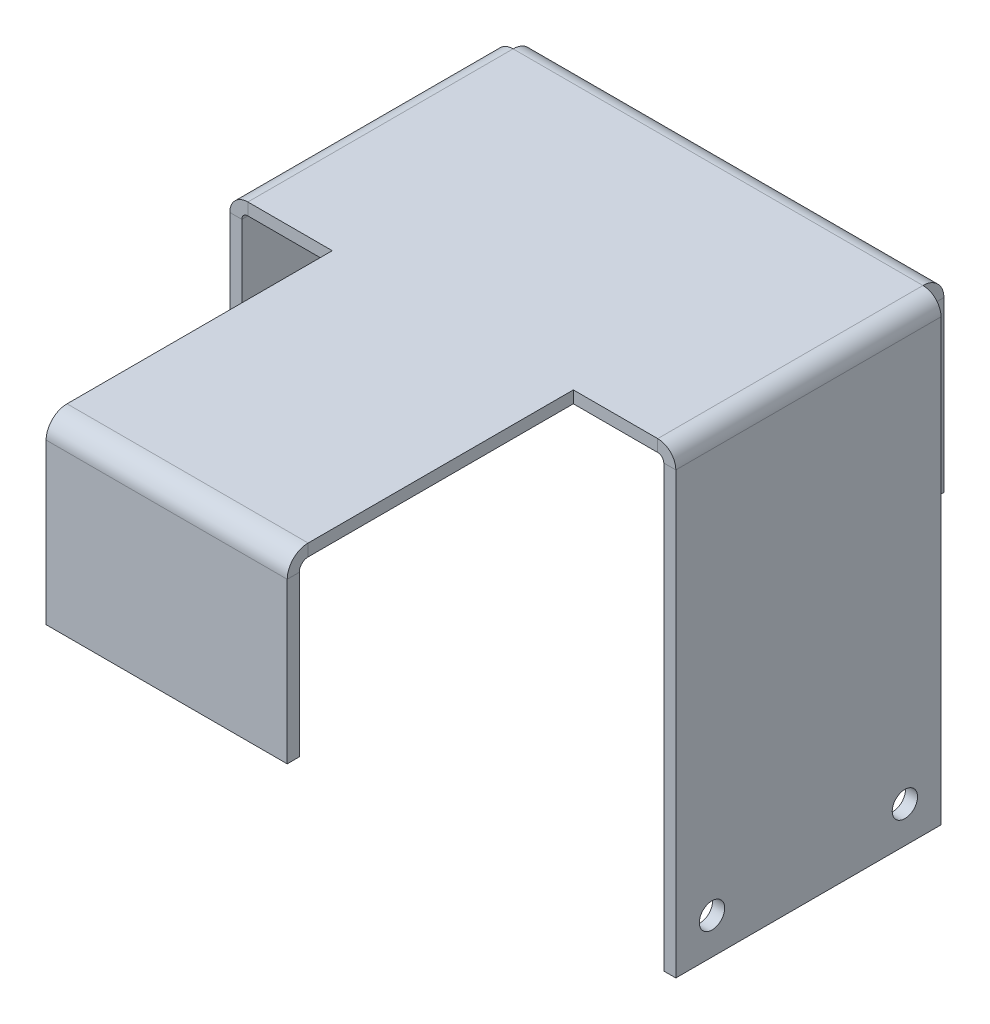
SolidWorks part; units mm, degrees
note: The reader was unsure of these and kept them because the rebuilt part matched: flange length of "边线-法兰1", "边线-法兰2", "边线-法兰3", "边线-法兰4", "边线-法兰5".
ref_plane "Front Plane" through (0, 0, 0) normal (0, 0, 1) x (1, 0, 0)
ref_plane "Top Plane" through (0, 0, 0) normal (0, 1, 0) x (1, 0, 0)
ref_plane "Right Plane" through (0, 0, 0) normal (1, 0, 0) x (0, 0, -1)
other "Configuration Table"
sketch "草图1" plane through (0, 0, 0) normal (0, 1, 0) x (1, 0, 0)
  line L1 (-17.5, 11) -> (17.5, 11)
  line L2 (-17.5, 11) -> (-17.5, -11)
  line L3 (-17.5, -11) -> (17.5, -11)
  line L4 (17.5, 11) -> (17.5, -11)
  line L5 (-17.5, 11) -> (17.5, -11) construction
  line L6 (-17.5, -11) -> (17.5, 11) construction
  point P0 (0, 0)
  dimension "D1" = 35
  dimension "D2" = 22
base flange "基体-法兰1" sketch "草图1" thickness 1 reverse thickness direction no parameters "D1"=0.7366
edge flange "边线-法兰1" sketch "草图10" flange angle 90 flange length 20 flange position material outside bend radius 0.5 thickness 1 relief rectangular parameters "D6"=10
sketch "草图10" plane through (-17.5, -1, 0) normal (1, 0, 0) x (0, 0, 1)
  line L2 (-11, 0) -> (-11, 19)
  line L3 (-11, 19) -> (11, 19)
  line L4 (11, 19) -> (11, 0)
  line L13 (11, 0) -> (-11, 0) construction
  line L14 (11, 0) -> (-11, 0)
bend "边线折弯1" bend radius 0.5 bend angle 90 parameters "D5"=1
edge flange "边线-法兰2" sketch "草图13" flange angle 90 flange length 38 flange position material outside bend radius 0.5 thickness 1 relief rectangular parameters "D6"=10
sketch "草图13" plane through (17.5, -1, 0) normal (-1, 0, 0) x (0, 0, -1)
  line L2 (-11, 0) -> (-11, 37)
  line L3 (-11, 37) -> (11, 37)
  line L4 (11, 37) -> (11, 0)
  line L5 (11, 0) -> (-11, 0) construction
  line L6 (11, 0) -> (-11, 0)
bend "边线折弯2" bend radius 0.5 bend angle 90 parameters "D5"=2
edge flange "边线-法兰3" sketch "草图16" flange angle 90 flange length 15.7366 flange position bend outside bend radius 0.7366 thickness 1 relief rectangular parameters "D6"=10
sketch "草图16" plane through (0, -1, -11) normal (0, 0, -1) x (1, 0, 0)
  line L0 (17, 0) -> (-17, 0) construction
  line L1 (17, 0) -> (-17, 0)
  line L2 (-17, 0) -> (-17, 14.7366)
  line L3 (-17, 14.7366) -> (17, 14.7366)
  line L4 (17, 14.7366) -> (17, 0)
bend "边线折弯3" bend radius 0.7366 bend angle 90 parameters "D5"=3
sketch "草图19" plane through (0, 0, 11) normal (0, 0, 1) x (1, 0, 0)
  line L0 (0, 0) -> (10, 0)
  line L1 (-17, 0) -> (17, 0) construction
  line L2 (10, 0) -> (10, -1)
  line L3 (-17, -1) -> (17, -1) construction
  line L4 (10, -1) -> (-10, -1)
  line L5 (-10, -1) -> (-10, 0)
  line L6 (-10, 0) -> (0, 0)
  dimension "D1" = 10
  dimension "D2" = 10
extrude "凸台-拉伸1" add sketch "草图19" along normal blind 22
edge flange "边线-法兰4" sketch "草图22" flange angle 90 flange length 15 flange position bend outside bend radius 0.7366 thickness 1 relief rectangular parameters "D6"=10
sketch "草图22" plane through (0, -1, 33) normal (0, 0, -1) x (1, 0, 0)
  line L2 (-10, 0) -> (-10, 14)
  line L3 (-10, 14) -> (10, 14)
  line L4 (10, 14) -> (10, 0)
  line L5 (10, 0) -> (-10, 0) construction
  line L6 (10, 0) -> (-10, 0)
bend "边线折弯4" bend radius 0.7366 bend angle 90 parameters "D5"=4
edge flange "边线-法兰5" sketch "草图25" flange angle 150 flange length 9 flange position material outside bend radius 0.7366 thickness 1 relief rectangular parameters "D6"=10
sketch "草图25" plane through (-18.5, -20, 0) normal (0.866, -0.5, 0) x (0, 0, 1)
  line L2 (-11, 0) -> (-11, 8.7321)
  line L3 (-11, 8.7321) -> (11, 8.7321)
  line L4 (11, 8.7321) -> (11, 0)
  line L15 (11, 0) -> (-11, 0) construction
  line L16 (11, 0) -> (-11, 0)
bend "边线折弯5" bend radius 0.7366 bend angle 30 parameters "D5"=5
sketch "草图26" plane through (-5.2147, 3.0107, 0) normal (-0.866, 0.5, 0) x (0, 0, 1)
  line L0 (-4.3, -31.1026) -> (4.3, -31.1026) construction
  line L1 (-4.3, -29.9026) -> (4.3, -29.9026)
  line L2 (-4.3, -32.3026) -> (4.3, -32.3026)
  line L3 (11, -35.3026) -> (-11, -35.3026) construction
  line L6 (0, -26.7679) -> (0, -35.3026) construction
  line L7 (-11, -26.7679) -> (11, -26.7679) construction
  arc A0 (-4.3, -29.9026) -> (-4.3, -32.3026) centre (-4.3, -31.1026) ccw
  arc A1 (4.3, -32.3026) -> (4.3, -29.9026) centre (4.3, -31.1026) ccw
  point P2 (0, -31.1026)
  point P7 (-5.5, -31.1026)
  point P8 (5.5, -31.1026)
  point P11 (0, 0)
  dimension "D1" = 11
  dimension "D2" = 1.2
  dimension "D3" = 3
extrude "切除-拉伸1" cut sketch "草图26" against normal blind 22 normal cut yes
sketch "草图27" plane through (18.5, 0, 0) normal (1, 0, 0) x (0, 0, -1)
  line L0 (11, -38) -> (-11, -38) construction
  line L2 (-11, -38) -> (-11, -1.5) construction
  line L3 (11, -1.5) -> (11, -38) construction
  circle A0 centre (8, -35) radius 1.05
  circle A1 centre (-8, -35) radius 1.05
  point P8 (-8.7499, -32.5047)
  dimension "D3" = 2.1
  dimension "D1" = 3
  dimension "D2" = 3
  dimension "D4" = 3
  dimension "D5" = 3
extrude "切除-拉伸2" cut sketch "草图27" against normal blind 22 normal cut yes
sketch "折弯-线1" [suppressed] plane through (0, 0, 0) normal (0, 1, 0) x (1, 0, 0)
sketch "边界框1" [suppressed] plane through (0, 0, 0) normal (0, 1, 0) x (1, 0, 0)
sheet metal parameters "钣金2" thickness 1 parameters "D1"=0.7366
flat pattern "平板型式2" [suppressed]
sketch "折弯-线2" plane through (0, 0, 0) normal (0, 1, 0) x (1, 0, 0)
sketch3d "边界框2" [suppressed]
  line L0 (-16.5, -10, 0) -> (16.5, -10, 0) construction
  line L1 (-16.5, 10, 0) -> (16.5, 10, 0) construction
  line L2 (-16.5, -10, 0) -> (-16.5, 10, 0) construction
  line L3 (16.5, -10, 0) -> (16.5, 10, 0) construction
sheet metal parameters "钣金3" thickness 1 parameters "D1"=0.7366
flat pattern "平板型式2"
sketch "折弯-线2" plane through (0, 0, 0) normal (0, 1, 0) x (1, 0, 0)
  line L0 (-16.499, 10) -> (-16.499, -10) construction
  line L1 (-16.499, 10) -> (-16.499, -10) construction
sketch3d "边界框2" [suppressed]
  line L0 (16.5, -10, 0) -> (-21.498, -10, 0) construction
  line L1 (16.5, 10, 0) -> (-21.498, 10, 0) construction
  line L2 (16.5, -10, 0) -> (16.5, 10, 0) construction
  line L3 (-21.498, -10, 0) -> (-21.498, 10, 0) construction
bend of the flat pattern "展平-<边线折弯1>1"
sheet metal parameters "钣金4" thickness 1 parameters "D1"=0.7366
flat pattern "平板型式2"
sketch "折弯-线2" plane through (0, 0, 0) normal (0, 1, 0) x (1, 0, 0)
  line L0 (-17.5498, 12) -> (-17.5498, -12) construction
  line L1 (-17.5498, 12) -> (-17.5498, -12) construction
  line L2 (17.7854, -12) -> (17.7854, 12) construction
  line L3 (17.7854, -12) -> (17.7854, 12) construction
sketch3d "边界框2" [suppressed]
  line L0 (47.0708, -12, 0) -> (-41.5996, -12, 0) construction
  line L1 (47.0708, 12, 0) -> (-41.5996, 12, 0) construction
  line L2 (47.0708, -12, 0) -> (47.0708, 12, 0) construction
  line L3 (-41.5996, -12, 0) -> (-41.5996, 12, 0) construction
bend of the flat pattern "展平-<边线折弯1>1"
bend of the flat pattern "展平-<边线折弯2>1"
sheet metal parameters "钣金5" thickness 1 parameters "D1"=0.7366
flat pattern "平板型式2"
sketch "折弯-线2" plane through (0, 0, 0) normal (0, 1, 0) x (1, 0, 0)
  line L0 (-17.5498, 12) -> (-17.5498, -12) construction
  line L1 (-17.5498, 12) -> (-17.5498, -12) construction
  line L2 (17.7854, -12) -> (17.7854, 12) construction
  line L3 (17.7854, -12) -> (17.7854, 12) construction
  line L4 (17, 12.9712) -> (-17, 12.9712) construction
  line L5 (17, 12.9712) -> (-17, 12.9712) construction
sketch3d "边界框2" [suppressed]
  line L0 (47.0708, -12, 0) -> (-41.5996, -12, 0) construction
  line L1 (47.0708, 25.9424, 0) -> (-41.5996, 25.9424, 0) construction
  line L2 (47.0708, -12, 0) -> (47.0708, 25.9424, 0) construction
  line L3 (-41.5996, -12, 0) -> (-41.5996, 25.9424, 0) construction
bend of the flat pattern "展平-<边线折弯1>1"
bend of the flat pattern "展平-<边线折弯2>1"
bend of the flat pattern "展平-<边线折弯3>1"
sheet metal parameters "钣金6" thickness 1 parameters "D1"=0.7366
flat pattern "平板型式2"
sketch "折弯-线2" plane through (0, 0, 0) normal (0, 1, 0) x (1, 0, 0)
  line L0 (-17.5498, 11) -> (-17.5498, -11) construction
  line L1 (-17.5498, 11) -> (-17.5498, -11) construction
  line L2 (17.7854, -11) -> (17.7854, 11) construction
  line L3 (17.7854, -11) -> (17.7854, 11) construction
  line L4 (17, 11.9712) -> (-17, 11.9712) construction
  line L5 (17, 11.9712) -> (-17, 11.9712) construction
sketch3d "边界框2" [suppressed]
  line L0 (47.0708, -33, 0) -> (-41.5996, -33, 0) construction
  line L1 (47.0708, 24.9424, 0) -> (-41.5996, 24.9424, 0) construction
  line L2 (47.0708, -33, 0) -> (47.0708, 24.9424, 0) construction
  line L3 (-41.5996, -33, 0) -> (-41.5996, 24.9424, 0) construction
bend of the flat pattern "展平-<边线折弯1>1"
bend of the flat pattern "展平-<边线折弯2>1"
bend of the flat pattern "展平-<边线折弯3>1"
sheet metal parameters "钣金7" thickness 1 parameters "D1"=0.7366
flat pattern "平板型式2"
sketch "折弯-线2" plane through (0, 0, 0) normal (0, 1, 0) x (1, 0, 0)
  line L0 (-17.5498, 11) -> (-17.5498, -11) construction
  line L1 (-17.5498, 11) -> (-17.5498, -11) construction
  line L2 (17.7854, -11) -> (17.7854, 11) construction
  line L3 (17.7854, -11) -> (17.7854, 11) construction
  line L4 (17, 11.9712) -> (-17, 11.9712) construction
  line L5 (17, 11.9712) -> (-17, 11.9712) construction
  line L6 (-10, -33.9712) -> (10, -33.9712) construction
  line L7 (-10, -33.9712) -> (10, -33.9712) construction
sketch3d "边界框2" [suppressed]
  line L0 (61.2925, -6.4841, 0) -> (-2.0363, -57.9963, 0) construction
  line L1 (13.7547, 51.9586, 0) -> (-49.5741, 0.4464, 0) construction
  line L2 (61.2925, -6.4841, 0) -> (13.7547, 51.9586, 0) construction
  line L3 (-2.0363, -57.9963, 0) -> (-49.5741, 0.4464, 0) construction
bend of the flat pattern "展平-<边线折弯1>1"
bend of the flat pattern "展平-<边线折弯2>1"
bend of the flat pattern "展平-<边线折弯3>1"
bend of the flat pattern "展平-<边线折弯4>1"
sheet metal parameters "钣金8" thickness 1 parameters "D1"=0.7366
flat pattern "平板型式2"
sketch "折弯-线2" plane through (0, 0, 0) normal (0, 1, 0) x (1, 0, 0)
  line L0 (-17.5498, 11) -> (-17.5498, -11) construction
  line L1 (-17.5498, 11) -> (-17.5498, -11) construction
  line L2 (17.7854, -11) -> (17.7854, 11) construction
  line L3 (17.7854, -11) -> (17.7854, 11) construction
  line L4 (17, 11.9712) -> (-17, 11.9712) construction
  line L5 (17, 11.9712) -> (-17, 11.9712) construction
  line L6 (-10, -33.9712) -> (10, -33.9712) construction
  line L7 (-10, -33.9712) -> (10, -33.9712) construction
  line L8 (-36.7259, 11) -> (-36.7259, -11) construction
  line L9 (-36.7259, 11) -> (-36.7259, -11) construction
sketch3d "边界框2" [suppressed]
  line L0 (58.9343, -1.4041, 0) -> (-0.4453, -58.1959, 0) construction
  line L1 (2.8062, 57.2816, 0) -> (-56.5734, 0.4898, 0) construction
  line L2 (58.9343, -1.4041, 0) -> (2.8062, 57.2816, 0) construction
  line L3 (-0.4453, -58.1959, 0) -> (-56.5734, 0.4898, 0) construction
bend of the flat pattern "展平-<边线折弯1>1"
bend of the flat pattern "展平-<边线折弯2>1"
bend of the flat pattern "展平-<边线折弯3>1"
bend of the flat pattern "展平-<边线折弯4>1"
bend of the flat pattern "展平-<边线折弯5>1"
sheet metal parameters "钣金9" thickness 1 parameters "D1"=0.7366
flat pattern "平板型式2"
sketch "折弯-线2" plane through (0, 0, 0) normal (0, 1, 0) x (1, 0, 0)
  line L0 (-17.5498, 11) -> (-17.5498, -11) construction
  line L1 (-17.5498, 11) -> (-17.5498, -11) construction
  line L2 (17.7854, -11) -> (17.7854, 11) construction
  line L3 (17.7854, -11) -> (17.7854, 11) construction
  line L4 (17, 11.9712) -> (-17, 11.9712) construction
  line L5 (17, 11.9712) -> (-17, 11.9712) construction
  line L6 (-10, -33.9712) -> (10, -33.9712) construction
  line L7 (-10, -33.9712) -> (10, -33.9712) construction
  line L8 (-36.7259, 11) -> (-36.7259, -11) construction
  line L9 (-36.7259, 11) -> (-36.7259, -11) construction
sketch3d "边界框2" [suppressed]
  line L0 (65.8716, -2.084, 0) -> (-4.7914, -60.4161, 0) construction
  line L1 (14.2779, 60.4161, 0) -> (-56.3851, 2.084, 0) construction
  line L2 (65.8716, -2.084, 0) -> (14.2779, 60.4161, 0) construction
  line L3 (-4.7914, -60.4161, 0) -> (-56.3851, 2.084, 0) construction
bend of the flat pattern "展平-<边线折弯1>1"
bend of the flat pattern "展平-<边线折弯2>1"
bend of the flat pattern "展平-<边线折弯3>1"
bend of the flat pattern "展平-<边线折弯4>1"
bend of the flat pattern "展平-<边线折弯5>1"
sheet metal parameters "钣金10" thickness 1 parameters "D1"=0.7366
flat pattern "平板型式2"
sketch "折弯-线2" plane through (0, 0, 0) normal (0, 1, 0) x (1, 0, 0)
  line L0 (-17.5498, 11) -> (-17.5498, -11) construction
  line L1 (-17.5498, 11) -> (-17.5498, -11) construction
  line L2 (17.7854, -11) -> (17.7854, 11) construction
  line L3 (17.7854, -11) -> (17.7854, 11) construction
  line L4 (17, 11.9712) -> (-17, 11.9712) construction
  line L5 (17, 11.9712) -> (-17, 11.9712) construction
  line L6 (-10, -33.9712) -> (10, -33.9712) construction
  line L7 (-10, -33.9712) -> (10, -33.9712) construction
  line L8 (-36.7259, 11) -> (-36.7259, -11) construction
  line L9 (-36.7259, 11) -> (-36.7259, -11) construction
sketch3d "边界框2" [suppressed]
  line L0 (65.8716, -2.084, 0) -> (-4.7914, -60.4161, 0) construction
  line L1 (14.2779, 60.4161, 0) -> (-56.3851, 2.084, 0) construction
  line L2 (65.8716, -2.084, 0) -> (14.2779, 60.4161, 0) construction
  line L3 (-4.7914, -60.4161, 0) -> (-56.3851, 2.084, 0) construction
bend of the flat pattern "展平-<边线折弯1>1"
bend of the flat pattern "展平-<边线折弯2>1"
bend of the flat pattern "展平-<边线折弯3>1"
bend of the flat pattern "展平-<边线折弯4>1"
bend of the flat pattern "展平-<边线折弯5>1"
